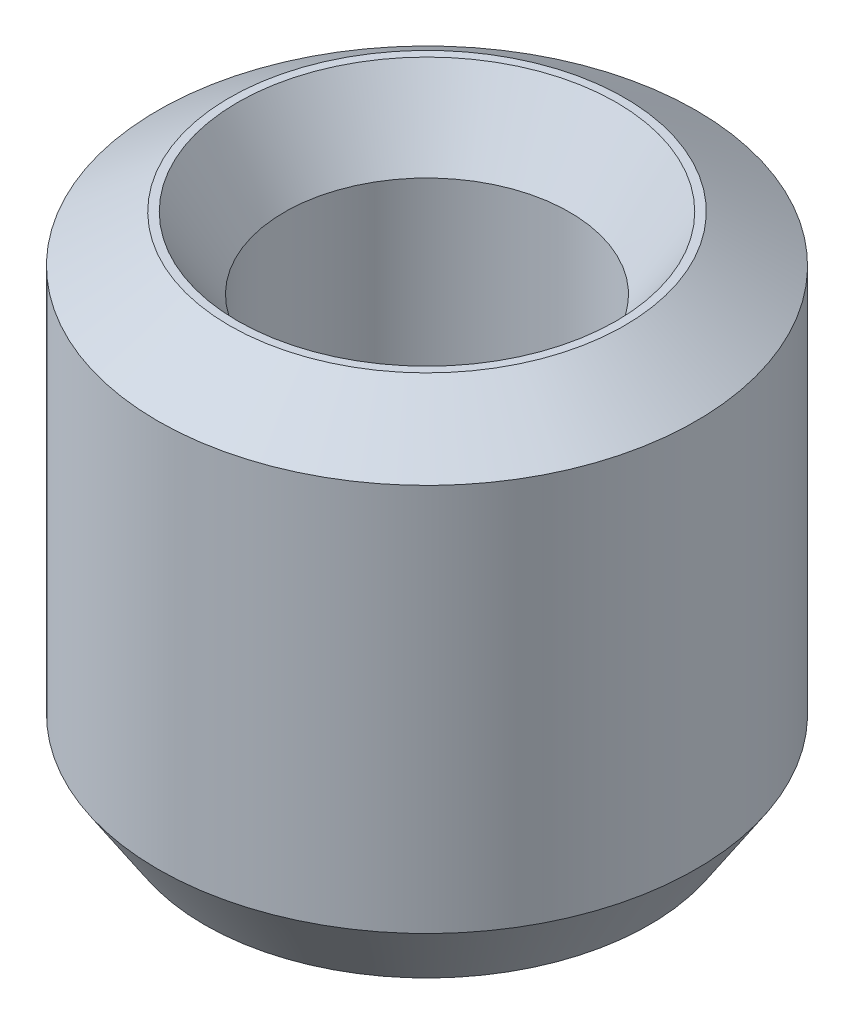
SolidWorks part; units mm, degrees
ref_plane "Front Plane" through (0, 0, 0) normal (0, 0, 1) x (1, 0, 0)
ref_plane "Top Plane" through (0, 0, 0) normal (0, 1, 0) x (1, 0, 0)
ref_plane "Right Plane" through (0, 0, 0) normal (1, 0, 0) x (0, 0, -1)
sketch "Sketch1" plane through (0, 0, 0) normal (0, 1, 0) x (1, 0, 0)
  circle A0 centre (0, 0) radius 20
  dimension "SLEEVE_OD" = 40
extrude "Boss-Extrude1" add sketch "Sketch1" along normal blind 37.642
sketch "Sketch2" plane through (0, 0, 0) normal (0, 1, 0) x (1, 0, 0)
  circle A0 centre (0, 0) radius 10.5918
  dimension "BORE_D" = 21.1837
extrude "Cut-Extrude1" cut sketch "Sketch2" along normal through all
chamfer "Chamfer1" distance 3.4788 angle 56.833 4 edges at (0, 37.642, 10.5918) (0, 0, 10.5918) (0, 0, 20) (0, 37.642, 20) first distance on face at (0, 37.642, 10.5918) first distance on face at (0, 0, 10.5918) first distance on face at (0, 37.642, 20)
